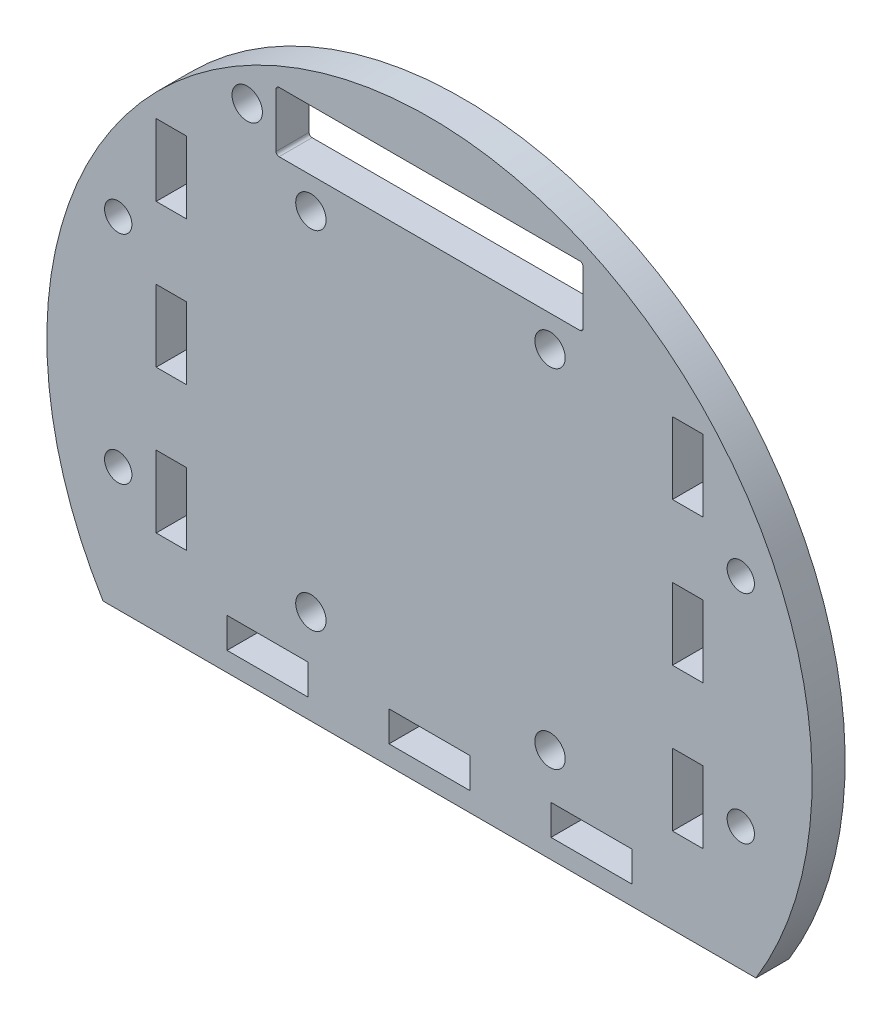
SolidWorks part; units mm, degrees
material "ABS"
ref_plane "Front Plane" through (0, 0, 0) normal (0, 0, 1) x (1, 0, 0)
ref_plane "Top Plane" through (0, 0, 0) normal (0, 1, 0) x (1, 0, 0)
ref_plane "Right Plane" through (0, 0, 0) normal (1, 0, 0) x (0, 0, -1)
sketch "Sketch1" plane through (0, 0, 0) normal (0, 0, 1) x (1, 0, 0)
  line L0 (-53.7502, -32.8621) -> (53.7502, -32.8621) construction
  line L1 (-53.7502, -32.8621) -> (53.7502, -32.8621)
  line L4 (20, -29.6871) -> (33.3333, -29.6871)
  line L5 (20, -24.6913) -> (20, -29.6871)
  line L6 (33.3333, -24.6913) -> (20, -24.6913)
  line L7 (33.3333, -29.6871) -> (33.3333, -24.6913)
  line L8 (20, -29.6871) -> (33.3333, -29.6871)
  line L9 (20, -24.6913) -> (20, -29.6871)
  line L10 (33.3333, -24.6913) -> (20, -24.6913)
  line L11 (33.3333, -29.6871) -> (33.3333, -24.6913)
  line L12 (-6.6667, -29.6871) -> (6.6667, -29.6871)
  line L13 (-6.6667, -24.6913) -> (-6.6667, -29.6871)
  line L14 (6.6667, -24.6913) -> (-6.6667, -24.6913)
  line L15 (6.6667, -29.6871) -> (6.6667, -24.6913)
  line L16 (-6.6667, -29.6871) -> (6.6667, -29.6871)
  line L17 (-6.6667, -24.6913) -> (-6.6667, -29.6871)
  line L18 (6.6667, -24.6913) -> (-6.6667, -24.6913)
  line L19 (6.6667, -29.6871) -> (6.6667, -24.6913)
  line L20 (-33.3333, -29.6871) -> (-20, -29.6871)
  line L21 (-33.3333, -24.6913) -> (-33.3333, -29.6871)
  line L22 (-20, -24.6913) -> (-33.3333, -24.6913)
  line L23 (-20, -29.6871) -> (-20, -24.6913)
  line L24 (-33.3333, -29.6871) -> (-20, -29.6871)
  line L25 (-33.3333, -24.6913) -> (-33.3333, -29.6871)
  line L26 (-20, -24.6913) -> (-33.3333, -24.6913)
  line L27 (-20, -29.6871) -> (-20, -24.6913)
  line L28 (-44.9958, -18.7822) -> (-40, -18.7822)
  line L29 (-44.9958, -6.964) -> (-44.9958, -18.7822)
  line L30 (-40, -6.964) -> (-44.9958, -6.964)
  line L31 (-40, -18.7822) -> (-40, -6.964)
  line L32 (-44.9958, -18.7822) -> (-40, -18.7822)
  line L33 (-44.9958, -6.964) -> (-44.9958, -18.7822)
  line L34 (-40, -6.964) -> (-44.9958, -6.964)
  line L35 (-40, -18.7822) -> (-40, -6.964)
  line L36 (-40, 16.6724) -> (-44.9958, 16.6724)
  line L37 (-40, 4.8542) -> (-40, 16.6724)
  line L38 (-44.9958, 4.8542) -> (-40, 4.8542)
  line L39 (-44.9958, 16.6724) -> (-44.9958, 4.8542)
  line L40 (-40, 16.6724) -> (-44.9958, 16.6724)
  line L41 (-40, 4.8542) -> (-40, 16.6724)
  line L42 (-44.9958, 4.8542) -> (-40, 4.8542)
  line L43 (-44.9958, 16.6724) -> (-44.9958, 4.8542)
  line L44 (-40, 40.3087) -> (-44.9958, 40.3087)
  line L45 (-40, 28.4905) -> (-40, 40.3087)
  line L46 (-44.9958, 28.4905) -> (-40, 28.4905)
  line L47 (-44.9958, 40.3087) -> (-44.9958, 28.4905)
  line L48 (-40, 40.3087) -> (-44.9958, 40.3087)
  line L49 (-40, 28.4905) -> (-40, 40.3087)
  line L50 (-44.9958, 28.4905) -> (-40, 28.4905)
  line L51 (-44.9958, 40.3087) -> (-44.9958, 28.4905)
  line L52 (44.9958, -6.964) -> (40, -6.964)
  line L53 (44.9958, -18.7822) -> (44.9958, -6.964)
  line L54 (40, -18.7822) -> (44.9958, -18.7822)
  line L55 (40, -6.964) -> (40, -18.7822)
  line L56 (44.9958, -6.964) -> (40, -6.964)
  line L57 (44.9958, -18.7822) -> (44.9958, -6.964)
  line L58 (40, -18.7822) -> (44.9958, -18.7822)
  line L59 (40, -6.964) -> (40, -18.7822)
  line L60 (40, 4.8542) -> (44.9958, 4.8542)
  line L61 (40, 16.6724) -> (40, 4.8542)
  line L62 (44.9958, 16.6724) -> (40, 16.6724)
  line L63 (44.9958, 4.8542) -> (44.9958, 16.6724)
  line L64 (40, 4.8542) -> (44.9958, 4.8542)
  line L65 (40, 16.6724) -> (40, 4.8542)
  line L66 (44.9958, 16.6724) -> (40, 16.6724)
  line L67 (44.9958, 4.8542) -> (44.9958, 16.6724)
  line L68 (40, 28.4905) -> (44.9958, 28.4905)
  line L69 (40, 40.3087) -> (40, 28.4905)
  line L70 (44.9958, 40.3087) -> (40, 40.3087)
  line L71 (44.9958, 28.4905) -> (44.9958, 40.3087)
  line L72 (40, 28.4905) -> (44.9958, 28.4905)
  line L73 (40, 40.3087) -> (40, 28.4905)
  line L74 (44.9958, 40.3087) -> (40, 40.3087)
  line L75 (44.9958, 28.4905) -> (44.9958, 40.3087)
  line L76 (25.265, 45.4834) -> (25.265, 54.3734)
  line L77 (-24.765, 44.9834) -> (24.765, 44.9834)
  line L78 (-25.265, 54.3734) -> (-25.265, 45.4834)
  line L79 (24.765, 54.8734) -> (-24.765, 54.8734)
  line L80 (25.265, 45.4834) -> (25.265, 54.3734)
  line L81 (-24.765, 44.9834) -> (24.765, 44.9834)
  line L82 (-25.265, 54.3734) -> (-25.265, 45.4834)
  line L83 (24.765, 54.8734) -> (-24.765, 54.8734)
  arc A0 (53.7502, -32.8621) -> (-53.7502, -32.8621) centre (0, 0) ccw construction
  circle A1 centre (-51.25, 23.184) radius 2.25
  circle A2 centre (-51.25, 23.184) radius 2.25
  circle A3 centre (19.8443, 39.8334) radius 1.65 construction
  circle A5 centre (-51.25, -12.4964) radius 2.25
  circle A6 centre (-51.25, -12.4964) radius 2.25
  circle A7 centre (-30.0111, 49.9284) radius 2.5
  circle A8 centre (-30.0111, 49.9284) radius 2.5
  circle A9 centre (51.25, 23.184) radius 2.25
  circle A10 centre (51.25, 23.184) radius 2.25
  circle A11 centre (19.8443, -17.3166) radius 1.65 construction
  circle A13 centre (51.25, -12.4964) radius 2.25
  circle A14 centre (51.25, -12.4964) radius 2.25
  circle A15 centre (-19.5257, -17.3166) radius 1.65 construction
  arc A17 (53.7502, -32.8621) -> (-53.7502, -32.8621) centre (0, 0) ccw
  circle A18 centre (-19.5257, 39.8334) radius 1.65 construction
  circle A19 centre (19.8443, 39.8334) radius 1.65 construction
  arc A20 (24.765, 44.9834) -> (25.265, 45.4834) centre (24.765, 45.4834) ccw
  arc A21 (-25.265, 45.4834) -> (-24.765, 44.9834) centre (-24.765, 45.4834) ccw
  arc A22 (-24.765, 54.8734) -> (-25.265, 54.3734) centre (-24.765, 54.3734) ccw
  arc A23 (25.265, 54.3734) -> (24.765, 54.8734) centre (24.765, 54.3734) ccw
  arc A24 (24.765, 44.9834) -> (25.265, 45.4834) centre (24.765, 45.4834) ccw
  arc A25 (-25.265, 45.4834) -> (-24.765, 44.9834) centre (-24.765, 45.4834) ccw
  arc A26 (-24.765, 54.8734) -> (-25.265, 54.3734) centre (-24.765, 54.3734) ccw
  arc A27 (25.265, 54.3734) -> (24.765, 54.8734) centre (24.765, 54.3734) ccw
  circle A28 centre (19.8443, -17.3166) radius 1.65 construction
  circle A29 centre (-19.5257, -17.3166) radius 1.65 construction
  circle A30 centre (-19.5257, 39.8334) radius 1.65 construction
  circle A31 centre (-19.5257, 39.8334) radius 2.5
  circle A32 centre (-19.5257, -17.3166) radius 2.5
  circle A33 centre (19.8443, -17.3166) radius 2.5
  circle A34 centre (19.8443, 39.8334) radius 2.5
  dimension "D1" = 0
  dimension "D2" = 0
  dimension "D3" = 0
  dimension "D4" = 0
  dimension "D6" = 0
  dimension "D7" = 0
  dimension "D8" = 0
  dimension "D9" = 0
  dimension "D10" = 0
  dimension "D11" = 0
  dimension "D13" = 0
  dimension "D14" = 0
  dimension "D15" = 0
  dimension "D16" = 0
  dimension "D18" = 0
extrude "Boss-Extrude1" add sketch "Sketch1" against normal blind 5.4356
